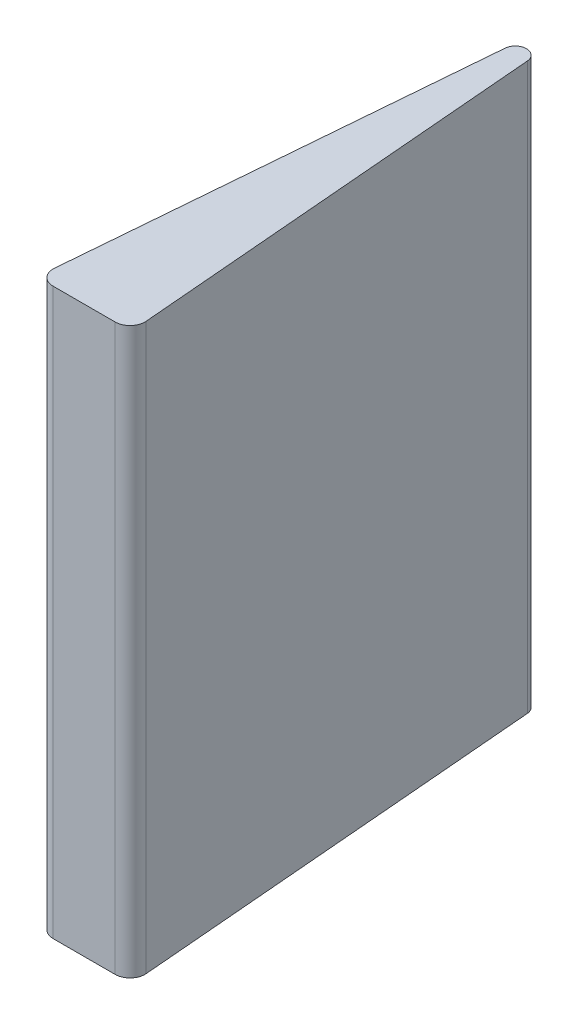
SolidWorks part; units mm, degrees
ref_plane "Top Plane" through (0, 0, 0) normal (0, 0, 1) x (1, 0, 0)
ref_plane "Front Plane" through (0, 0, 0) normal (0, 1, 0) x (1, 0, 0)
ref_plane "Right Plane" through (0, 0, 0) normal (1, 0, 0) x (0, 0, -1)
sketch "Sketch1" plane through (0, 0, 0) normal (0, 1, 0) x (1, 0, 0)
  line L0 (-61.7124, -98.3344) -> (-14.9479, 461.2492)
  line L2 (0, 0) -> (0, 438.7899) construction
  line L3 (-41.7818, -120) -> (41.7818, -120)
  line L5 (61.7124, -98.3344) -> (14.9479, 461.2492)
  arc A0 (-61.7124, -98.3344) -> (-41.7818, -120) centre (-41.7818, -100) ccw
  arc A1 (-14.9479, 461.2492) -> (14.9479, 461.2492) centre (0, 460) cw
  arc A2 (61.7124, -98.3344) -> (41.7818, -120) centre (41.7818, -100) cw
  point P6 (-61.3, -93.4)
  point P11 (0, 460)
  point P12 (61.3, -93.4)
  point P17 (0, -120)
  dimension "D3" = 20
  dimension "D4" = 15
  dimension "D1" = 580
  dimension "D2" = 26.6
  dimension "D5" = 61.3
  dimension "D6" = 120
extrude "Boss-Extrude1" add sketch "Sketch1" along normal blind 380 and the other way blind 380
ref_plane "Plane1" through (0, 0, -475) normal (0, 0, -1) x (-1, 0, 0)
ref_plane "Plane2" through (0, 0, -500) normal (0, 0, -1) x (-1, 0, 0)
ref_axis "Flap Rotation" through (0, -327.25, -500) along (0, 1, 0)
